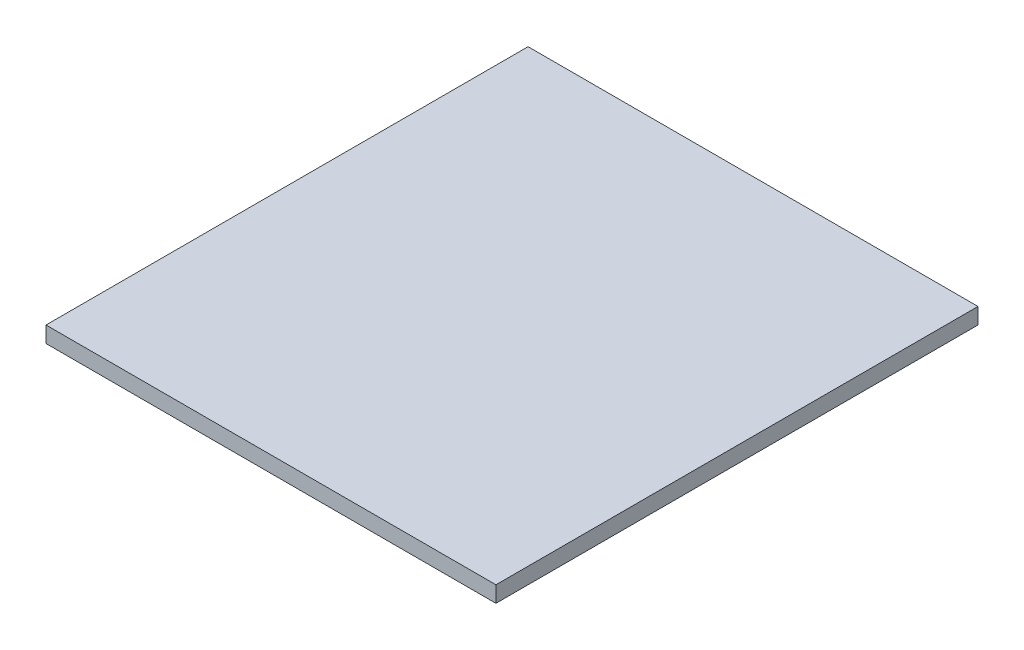
SolidWorks part; units mm, degrees
ref_plane "Спереди" through (0, 0, 0) normal (0, 0, 1) x (1, 0, 0)
ref_plane "Сверху" through (0, 0, 0) normal (0, 1, 0) x (1, 0, 0)
ref_plane "Справа" through (0, 0, 0) normal (1, 0, 0) x (0, 0, -1)
sketch "Эскиз1" plane through (0, 0, 0) normal (0, 1, 0) x (1, 0, 0)
  line L1 (0, 0) -> (280, 0)
  line L2 (0, 0) -> (0, 300)
  line L3 (0, 300) -> (280, 300)
  line L4 (280, 0) -> (280, 300)
  dimension "D1" = 280
  dimension "D2" = 300
extrude "Нижняя панель стола" add sketch "Эскиз1" along normal blind 10
